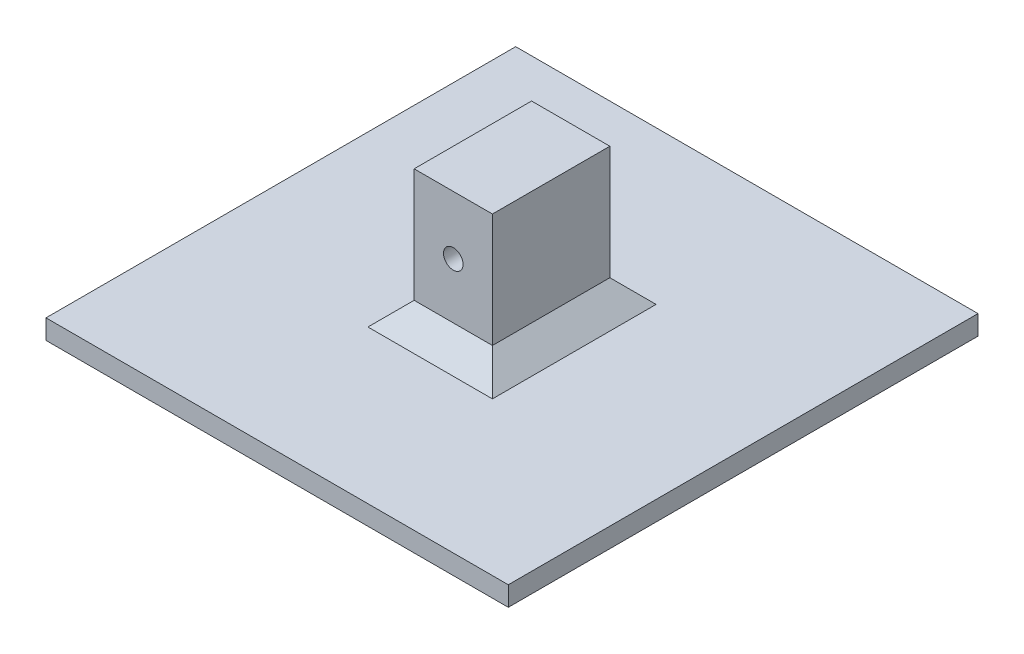
SolidWorks part; units mm, degrees
ref_plane "Front Plane" through (0, 0, 0) normal (0, 0, 1) x (1, 0, 0)
ref_plane "Top Plane" through (0, 0, 0) normal (0, 1, 0) x (1, 0, 0)
ref_plane "Right Plane" through (0, 0, 0) normal (1, 0, 0) x (0, 0, -1)
sketch "Sketch-Profile" plane through (0, 0, 0) normal (1, 0, 0) x (0, 0, -1)
  line L0 (-76.2, 6.35) -> (-76.2, 0)
  line L5 (-76.2, 6.35) -> (-19.05, 6.35)
  line L6 (-76.2, 0) -> (76.2, 0)
  line L7 (76.2, 6.35) -> (76.2, 0)
  line L8 (-76.2, 6.35) -> (76.2, 0) construction
  line L9 (-76.2, 0) -> (76.2, 6.35) construction
  line L10 (-19.05, 50.8) -> (-19.05, 6.35)
  line L11 (-19.05, 50.8) -> (19.05, 50.8)
  line L13 (19.05, 50.8) -> (19.05, 6.35)
  line L14 (-19.05, 50.8) -> (19.05, 6.35) construction
  line L15 (-19.05, 6.35) -> (19.05, 50.8) construction
  line L16 (19.05, 6.35) -> (76.2, 6.35)
  point P1 (0, 3.175)
  point P2 (0, 28.575)
  dimension "D1" = 6.35
  dimension "D2" = 50.8
  dimension "D3" = 152.4
  dimension "D4" = 38.1
extrude "Boss-Extrude1" add sketch "Sketch-Profile" along normal blind 12.7 and the other way blind 12.7
sketch "Sketch-Hole Location" plane through (0, 0, 19.05) normal (0, 0, 1) x (1, 0, 0)
  line L0 (0, 0) -> (0, 50.8) construction
  line L1 (12.7, 0) -> (-12.7, 0) construction
  line L2 (12.7, 50.8) -> (-12.7, 50.8) construction
  line L3 (118.2175, 31.8431) -> (31.7825, 31.8431) construction
  point P6 (0, 31.8431)
sketch "Sketch5" plane through (0, 0, 19.05) normal (0, 0, 1) x (1, 0, 0)
  point P0 (0, 31.8431)
hole_wizard "1/4 (0.25) Diameter Hole1" positions "Sketch5" profile "Sketch4" hole size "1/4" standard "ANSI Inch" end condition through all
sketch "Sketch4" plane through (0, 31.8431, 19.05) normal (1, 0, 0) x (0, -1, 0)
  line L0 (0, 0) -> (0, 95.25)
  line L1 (0, 95.25) -> (3.175, 95.25)
  line L2 (3.175, 95.25) -> (3.175, 0)
  line L5 (3.175, 0) -> (0, 0)
  line L11 (0, -6.35) -> (0, 107.95) construction
  dimension "Thru Hole Dia." = 6.35
  dimension "Thru Hole Depth" = 95.25
sketch "Sketch6" plane through (0, 0, 0) normal (1, 0, 0) x (0, 0, -1)
  line L0 (76.2, 0) -> (76.2, 6.35) construction
  line L1 (-76.2, 0) -> (76.2, 0) construction
  line L2 (-76.2, 6.35) -> (-76.2, 0) construction
  line L3 (76.2, 0) -> (76.2, 6.35)
  line L4 (-76.2, 0) -> (76.2, 0)
  line L5 (-76.2, 6.35) -> (-76.2, 0)
  line L6 (-76.2, 6.35) -> (76.2, 6.35)
extrude "Boss-Extrude2" add sketch "Sketch6" along normal blind 75 and the other way blind 75
chamfer "Chamfer1" distance 7.5 angle 45 4 edges at (0, 6.35, 19.05) (-12.7, 6.35, 0) (0, 6.35, -19.05) (12.7, 6.35, 0)
